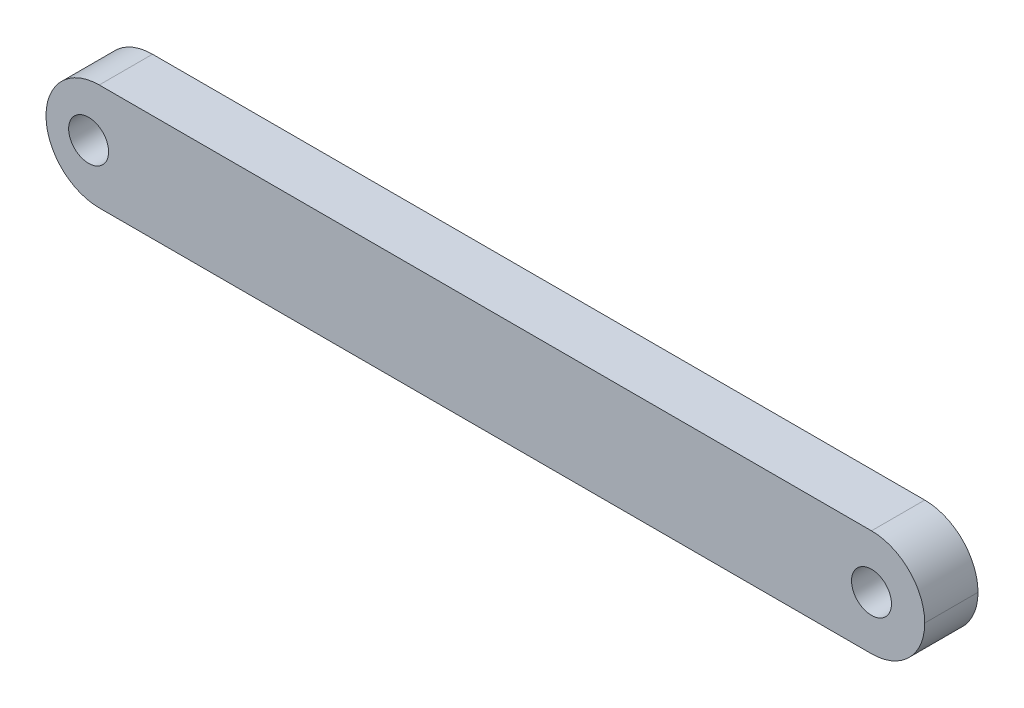
SolidWorks part; units mm, degrees
material "AISI 304"
ref_plane "Front Plane" through (0, 0, 0) normal (0, 0, 1) x (1, 0, 0)
ref_plane "Top Plane" through (0, 0, 0) normal (0, 1, 0) x (1, 0, 0)
ref_plane "Right Plane" through (0, 0, 0) normal (1, 0, 0) x (0, 0, -1)
sketch "Sketch1" plane through (0, 0, 0) normal (0, 1, 0) x (1, 0, 0)
  line L1 (104.775, -6.35) -> (-104.775, -6.35)
  line L2 (104.775, -6.35) -> (104.775, 6.35)
  line L3 (104.775, 6.35) -> (-104.775, 6.35)
  line L4 (-104.775, -6.35) -> (-104.775, 6.35)
  line L5 (104.775, -6.35) -> (-104.775, 6.35) construction
  line L6 (104.775, 6.35) -> (-104.775, -6.35) construction
  point P0 (0, 0)
  dimension "D1" = 12.7
  dimension "D2" = 209.55
extrude "Boss-Extrude1" add sketch "Sketch1" along normal mid plane 25.4
sketch "Sketch2" plane through (0, 0, 6.35) normal (0, 0, 1) x (1, 0, 0)
  line L0 (-104.775, 12.7) -> (-104.775, -12.7) construction
  line L1 (104.775, 12.7) -> (104.775, -12.7) construction
  circle A0 centre (-94.615, 0) radius 4.7625
  circle A1 centre (92.075, 0) radius 4.7625
  dimension "D1" = 9.525
  dimension "D2" = 10.16
  dimension "D3" = 12.7
extrude "Cut-Extrude1" cut sketch "Sketch2" against normal through all
fillet "Fillet1" radius 12.7 4 edges at (104.775, -12.7, 0) (104.775, 12.7, 0) (-104.775, -12.7, 0) (-104.775, 12.7, 0)
sketch "Sketch4" plane through (0, -12.7, 0) normal (0, -1, 0) x (1, 0, 0)
  line L0 (0, 0) -> (41.275, 0) construction
  line L1 (41.275, 0) -> (66.675, 0) construction
  line L3 (104.775, -6.35) -> (104.775, 6.35) construction
  circle A0 centre (41.275, 0) radius 3.175
  circle A1 centre (66.675, 0) radius 3.175
  dimension "D1" = 6.35
  dimension "D3" = 38.1
  dimension "D2" = 25.4
extrude "Cut-Extrude3" cut sketch "Sketch4" against normal blind 12.7
